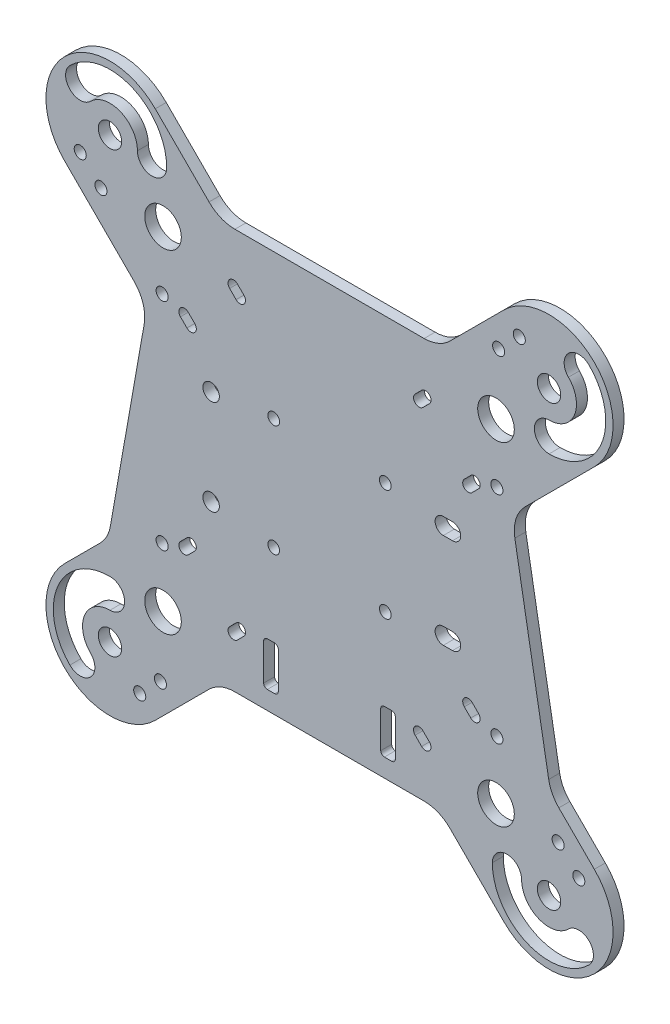
SolidWorks part; units mm, degrees
material "3.0205 (EN-AW 1200)"
ref_plane "Front" through (0, 0, 0) normal (0, 0, 1) x (1, 0, 0)
ref_plane "Top" through (0, 0, 0) normal (0, 1, 0) x (1, 0, 0)
ref_plane "Right" through (0, 0, 0) normal (1, 0, 0) x (0, 0, -1)
other "Massenmittelpunkt"
sketch "Skizze1" plane through (0, 0, 0) normal (0, 0, 1) x (1, 0, 0)
  line L0 (0, -54.3604) -> (0, 62.0087) construction
  line L1 (0, 0) -> (83.9041, 0) construction
  line L2 (30, 54.7487) -> (-30, 54.7487)
  line L3 (-30, 54.7487) -> (-47.6256, 72.3744)
  line L4 (47.6256, -72.3744) -> (30, -54.7487)
  line L5 (-72.3744, 47.6256) -> (-49.7487, 25)
  line L6 (-49.7487, 25) -> (-60.4524, -35.7037)
  line L7 (-60.4524, -35.7037) -> (-72.3744, -47.6256)
  line L8 (60.4524, -35.7037) -> (72.3744, -47.6256)
  line L9 (-47.6256, -72.3744) -> (-30, -54.7487)
  line L10 (-30, -54.7487) -> (30, -54.7487)
  line L11 (49.7487, 25) -> (60.4524, -35.7037)
  line L12 (72.3744, 47.6256) -> (49.7487, 25)
  line L13 (30, 54.7487) -> (47.6256, 72.3744)
  arc A0 (-47.6256, 72.3744) -> (-72.3744, 47.6256) centre (-60, 60) ccw
  arc A1 (-72.3744, -47.6256) -> (-47.6256, -72.3744) centre (-60, -60) ccw
  arc A2 (72.3744, -47.6256) -> (47.6256, -72.3744) centre (60, -60) cw
  arc A3 (47.6256, 72.3744) -> (72.3744, 47.6256) centre (60, 60) cw
  point P26 (0, -54.7487)
  point P35 (0, 54.7487)
  dimension "D5" = 17.5
  dimension "D7" = 17.5
  dimension "D1" = 120
  dimension "D2" = 120
  dimension "D3" = 120
  dimension "D4" = 30
  dimension "D6" = 45
  dimension "D8" = 10
  dimension "D9" = 30
  dimension "D10" = 60
  dimension "D11" = 31.9975
  dimension "D12" = 16.8602
extrude "Aufsatz-Linear austragen1" add sketch "Skizze1" along normal blind 3
sketch "Skizze2" plane through (0, 0, 3) normal (0, 0, 1) x (1, 0, 0)
  line L0 (0, 0) -> (-60, 60) construction
  line L1 (0, 0) -> (0, 84.3112) construction
  line L2 (0, 0) -> (70.8894, 0) construction
  line L3 (0, 0) -> (-60, -60) construction
  arc A0 (-47.6256, 72.3744) -> (-72.3744, 47.6256) centre (-60, 60) ccw construction
  arc A1 (-47.6256, 72.3744) -> (-72.3744, 47.6256) centre (-60, 60) ccw
  circle A2 centre (-60, 60) radius 3.2
  circle A3 centre (-45.5043, 45.5043) radius 5
  circle A4 centre (45.5043, 45.5043) radius 5
  circle A5 centre (60, 60) radius 3.2
  arc A7 (-72.3744, -47.6256) -> (-47.6256, -72.3744) centre (-60, -60) ccw construction
  arc A8 (-72.3744, -47.6256) -> (-47.6256, -72.3744) centre (-60, -60) ccw
  arc A9 (47.6256, -72.3744) -> (72.3744, -47.6256) centre (60, -60) ccw construction
  arc A10 (47.6256, -72.3744) -> (72.3744, -47.6256) centre (60, -60) ccw
  circle A11 centre (-60, -60) radius 3.2
  circle A13 centre (-45.5043, -45.5043) radius 5
  circle A14 centre (45.5043, -45.5043) radius 5
  circle A15 centre (60, -60) radius 3.2
  point P8 (-72.3744, 72.3744)
  point P24 (-72.3744, -72.3744)
  dimension "D1" = 6.4
  dimension "D2" = 10
  dimension "D4" = 6.4
  dimension "D5" = 10
  dimension "D3" = 38
  dimension "D6" = 38
extrude "Schnitt-Linear austragen1" cut sketch "Skizze2" against normal up to surface (3 mm away) contours A3 | A2 | A4 | A14 | A13 | A11 | A5 | A15 region at (-60, 60, 3) region at (-45.5043, 45.5043, 3) region at (45.5043, 45.5043, 3) region at (-60, -60, 3) region at (-45.5043, -45.5043, 3) region at (45.5043, -45.5043, 3) up to face at (0, -1.338, 0)
sketch "Skizze3" plane through (0, 0, 3) normal (0, 0, 1) x (1, 0, 0)
  line L0 (0, 0) -> (0, 66.0751) construction
  line L1 (0, 0) -> (91.439, 0) construction
  line L2 (-60, 60) -> (-93.2508, 93.2508) construction
  line L5 (-60, 60) -> (-28.4544, 60) construction
  line L6 (60, 60) -> (89.3075, 89.3075) construction
  line L7 (60, 60) -> (60, 26.1237) construction
  line L8 (60, -60) -> (74.6096, -74.6096) construction
  line L9 (-60, -60) -> (-91.9373, -91.9373) construction
  line L12 (60, -60) -> (20.7483, -60) construction
  line L13 (-60, -60) -> (-60, -22.984) construction
  arc A0 (65.3033, 65.3033) -> (70.9602, 70.9602) centre (68.1317, 68.1317) cw
  circle A1 centre (-60, 60) radius 3.2 construction
  circle A2 centre (-60, 60) radius 3.2
  arc A3 (-70.9602, 70.9602) -> (-44.5, 60) centre (-60, 60) cw
  arc A4 (-65.3033, 65.3033) -> (-52.5, 60) centre (-60, 60) cw
  arc A5 (-70.9602, 70.9602) -> (-65.3033, 65.3033) centre (-68.1317, 68.1317) ccw
  arc A6 (-52.5, 60) -> (-44.5, 60) centre (-48.5, 60) ccw
  arc A8 (60, 52.5) -> (65.3033, 65.3033) centre (60, 60) ccw
  arc A9 (60, 44.5) -> (60, 52.5) centre (60, 48.5) cw
  arc A10 (60, 44.5) -> (70.9602, 70.9602) centre (60, 60) ccw
  arc A12 (65.3033, -65.3033) -> (52.5, -60) centre (60, -60) cw
  arc A13 (70.9602, -70.9602) -> (44.5, -60) centre (60, -60) cw
  arc A14 (44.5, -60) -> (52.5, -60) centre (48.5, -60) cw
  arc A15 (65.3033, -65.3033) -> (70.9602, -70.9602) centre (68.1317, -68.1317) cw
  arc A16 (-70.9602, -70.9602) -> (-60, -44.5) centre (-60, -60) cw
  arc A17 (-65.3033, -65.3033) -> (-60, -52.5) centre (-60, -60) cw
  arc A18 (-70.9602, -70.9602) -> (-65.3033, -65.3033) centre (-68.1317, -68.1317) ccw
  arc A19 (-60, -44.5) -> (-60, -52.5) centre (-60, -48.5) cw
  dimension "D3" = 4
  dimension "D4" = 11.5
  dimension "D5" = 4
  dimension "D7" = 4
  dimension "D11" = 4
  dimension "D1" = 45
  dimension "D2" = 11.5
  dimension "D6" = 45
  dimension "D8" = 11.5
  dimension "D9" = 45
  dimension "D10" = 45
  dimension "D12" = 11.5
extrude "Schnitt-Linear austragen2" cut sketch "Skizze3" against normal up to surface (3 mm away) up to face at (-56.8, 60, 0)
ref_axis "Achse1" through (0, 0, -80.9) along (0, 0, 1)
sketch "Skizze5" plane through (0, 0, 3) normal (0, 0, 1) x (1, 0, 0)
  line L0 (31.11, -13) -> (33.61, -13) construction
  line L1 (-15.25, -15.25) -> (15.25, -15.25) construction
  line L2 (-15.25, -15.25) -> (-15.25, 15.25) construction
  line L3 (-15.25, 15.25) -> (15.25, 15.25) construction
  line L4 (15.25, -15.25) -> (15.25, 15.25) construction
  line L5 (-15.25, -15.25) -> (15.25, 15.25) construction
  line L6 (-15.25, 15.25) -> (15.25, -15.25) construction
  line L7 (-32.36, -13) -> (32.36, -13) construction
  line L8 (-32.36, -13) -> (-32.36, 13) construction
  line L9 (-32.36, 13) -> (32.36, 13) construction
  line L10 (32.36, -13) -> (32.36, 13) construction
  line L11 (-32.36, -13) -> (32.36, 13) construction
  line L12 (-32.36, 13) -> (32.36, -13) construction
  line L13 (31.11, 13) -> (33.61, 13) construction
  line L16 (31.11, 15.25) -> (33.61, 15.25)
  line L17 (31.11, 10.75) -> (33.61, 10.75)
  line L18 (31.11, -10.75) -> (33.61, -10.75)
  line L19 (31.11, -15.25) -> (33.61, -15.25)
  circle A0 centre (-15.25, 15.25) radius 1.6
  circle A1 centre (15.25, 15.25) radius 1.6
  circle A2 centre (15.25, -15.25) radius 1.6
  circle A3 centre (-15.25, -15.25) radius 1.6
  circle A4 centre (-32.36, 13) radius 2.25
  circle A7 centre (-32.36, -13) radius 2.25
  arc A10 (31.11, 15.25) -> (31.11, 10.75) centre (31.11, 13) ccw
  arc A11 (33.61, 10.75) -> (33.61, 15.25) centre (33.61, 13) ccw
  arc A12 (31.11, -10.75) -> (31.11, -15.25) centre (31.11, -13) ccw
  arc A13 (33.61, -15.25) -> (33.61, -10.75) centre (33.61, -13) ccw
  point P0 (0, 0)
  point P7 (0, 0)
  point P22 (32.36, 13)
  point P29 (32.36, -13)
  point P34 (28.86, 13)
  point P35 (35.86, 13)
  dimension "D3" = 3.2
  dimension "D4" = 4
  dimension "D7" = 4.5
  dimension "D8" = 4.5
  dimension "D9" = 4.5
  dimension "D11" = 7
  dimension "D1" = 30.5
  dimension "D2" = 30.5
  dimension "D5" = 64.72
  dimension "D6" = 26
extrude "Schnitt-Linear austragen3" cut sketch "Skizze5" against normal up to surface (3 mm away) up to face at (57.6646, -65.6381, 0)
sketch "Skizze6" plane through (0, 0, 3) normal (0, 0, 1) x (1, 0, 0)
  line L0 (-60, 60) -> (60, -60) construction
  line L1 (60, 60) -> (-60, -60) construction
ref_point "Punkt1"
ref_axis "Achse2" through (0, 0, 3) along (0, 0, 1)
sketch "Skizze7" plane through (0, 0, 3) normal (0, 0, 1) x (1, 0, 0)
  line L3 (-45.7487, 29.5) -> (45.7487, 29.5) construction
  line L5 (-45.7487, 29.5) -> (-45.7487, -29.5) construction
  line L9 (-45.7487, -29.5) -> (45.7487, -29.5) construction
  line L10 (45.7487, -29.5) -> (45.7487, 29.5) construction
  line L11 (0, 36.7682) -> (0, -20.7433) construction
  line L12 (0, 0) -> (-25.0088, 0) construction
  circle A8 centre (-45.7487, 29.5) radius 0.5
  circle A9 centre (-45.7487, -29.5) radius 0.5
  circle A10 centre (45.7487, -29.5) radius 0.5
  circle A11 centre (45.7487, 29.5) radius 0.5
  dimension "D3" = 1
  dimension "D1" = 4
  dimension "D2" = 59
extrude "Schnitt-Linear austragen4" cut sketch "Skizze7" against normal through all
fillet "Verrundung1" radius 10 8 edges at (-60.4524, -35.7037, 1.5) (-49.7487, 25, 1.5) (-30, 54.7487, 1.5) (30, 54.7487, 1.5) (60.4524, -35.7037, 1.5) (49.7487, 25, 1.5) (30, -54.7487, 1.5) (-30, -54.7487, 1.5)
sketch "Skizze8" plane through (0, 0, 3) normal (0, 0, 1) x (1, 0, 0)
  line L0 (72.3744, -72.3744) -> (-72.3744, 72.3744) construction
  line L1 (72.3744, 72.3744) -> (-72.3744, -72.3744) construction
  line L2 (20.2, -45.3527) -> (41.1281, -24.4247) construction
  line L3 (0, 14.4257) -> (0, -17.0343) construction
  line L4 (-16.3829, 0) -> (7.5205, 0) construction
  line L5 (-39.6707, -27.6499) -> (-37.9029, -25.8821) construction
  line L6 (24.4679, -39.3171) -> (26.2357, -41.0849) construction
  line L7 (25.5285, -38.2565) -> (27.2963, -40.0242)
  line L8 (23.4072, -40.3778) -> (25.175, -42.1456)
  line L9 (39.6707, -27.6499) -> (37.9029, -25.8821) construction
  line L10 (38.61, -28.7105) -> (36.8423, -26.9428)
  line L11 (40.7313, -26.5892) -> (38.9636, -24.8214)
  line L12 (-38.61, -28.7105) -> (-36.8423, -26.9428)
  line L13 (-40.7313, -26.5892) -> (-38.9636, -24.8214)
  line L14 (-24.4679, -39.3171) -> (-26.2357, -41.0849) construction
  line L15 (-25.5285, -38.2565) -> (-27.2963, -40.0242)
  line L16 (-23.4072, -40.3778) -> (-25.175, -42.1456)
  line L17 (-24.4679, 39.3171) -> (-26.2357, 41.0849) construction
  line L18 (-25.5285, 38.2565) -> (-27.2963, 40.0242)
  line L19 (-23.4072, 40.3778) -> (-25.175, 42.1456)
  line L20 (-39.6707, 27.6499) -> (-37.9029, 25.8821) construction
  line L21 (-38.61, 28.7105) -> (-36.8423, 26.9428)
  line L22 (-40.7313, 26.5892) -> (-38.9636, 24.8214)
  line L23 (39.6707, 27.6499) -> (37.9029, 25.8821) construction
  line L24 (38.61, 28.7105) -> (36.8423, 26.9428)
  line L25 (40.7313, 26.5892) -> (38.9636, 24.8214)
  line L26 (24.4679, 39.3171) -> (26.2357, 41.0849) construction
  line L27 (25.5285, 38.2565) -> (27.2963, 40.0242)
  line L28 (23.4072, 40.3778) -> (25.175, 42.1456)
  arc A0 (47.6256, -72.3744) -> (72.3744, -47.6256) centre (60, -60) ccw construction
  arc A1 (-47.6256, 72.3744) -> (-72.3744, 47.6256) centre (-60, 60) ccw construction
  arc A2 (72.3744, 47.6256) -> (47.6256, 72.3744) centre (60, 60) ccw construction
  arc A3 (-72.3744, -47.6256) -> (-47.6256, -72.3744) centre (-60, -60) ccw construction
  arc A18 (25.5285, -38.2565) -> (23.4072, -40.3778) centre (24.4679, -39.3171) ccw
  arc A19 (25.175, -42.1456) -> (27.2963, -40.0242) centre (26.2357, -41.0849) ccw
  arc A20 (38.61, -28.7105) -> (40.7313, -26.5892) centre (39.6707, -27.6499) ccw
  arc A21 (38.9636, -24.8214) -> (36.8423, -26.9428) centre (37.9029, -25.8821) ccw
  arc A22 (-38.61, -28.7105) -> (-40.7313, -26.5892) centre (-39.6707, -27.6499) cw
  arc A23 (-38.9636, -24.8214) -> (-36.8423, -26.9428) centre (-37.9029, -25.8821) cw
  arc A24 (-25.5285, -38.2565) -> (-23.4072, -40.3778) centre (-24.4679, -39.3171) cw
  arc A25 (-25.175, -42.1456) -> (-27.2963, -40.0242) centre (-26.2357, -41.0849) cw
  arc A26 (-25.5285, 38.2565) -> (-23.4072, 40.3778) centre (-24.4679, 39.3171) ccw
  arc A27 (-25.175, 42.1456) -> (-27.2963, 40.0242) centre (-26.2357, 41.0849) ccw
  arc A28 (-38.61, 28.7105) -> (-40.7313, 26.5892) centre (-39.6707, 27.6499) ccw
  arc A29 (-38.9636, 24.8214) -> (-36.8423, 26.9428) centre (-37.9029, 25.8821) ccw
  arc A30 (38.61, 28.7105) -> (40.7313, 26.5892) centre (39.6707, 27.6499) cw
  arc A31 (38.9636, 24.8214) -> (36.8423, 26.9428) centre (37.9029, 25.8821) cw
  arc A32 (25.5285, 38.2565) -> (23.4072, 40.3778) centre (24.4679, 39.3171) cw
  arc A33 (25.175, 42.1456) -> (27.2963, 40.0242) centre (26.2357, 41.0849) cw
  point P16 (0, 0)
  point P18 (25.3518, -40.201)
  point P21 (38.7868, -26.766)
  point P24 (45.5043, -45.5043)
  point P34 (-38.7868, -26.766)
  point P41 (-25.3518, -40.201)
  point P55 (-25.3518, 40.201)
  point P63 (-38.7868, 26.766)
  point P70 (38.7868, 26.766)
  point P77 (25.3518, 40.201)
  point P82 (23.4072, -38.2565)
  point P83 (27.2963, -42.1456)
  dimension "D2" = 5.5
  dimension "D1" = 3
  dimension "D3" = 18
  dimension "D5" = 9
  dimension "D4" = 16
extrude "ECSs Befestigung" cut sketch "Skizze8" against normal through all
sketch "Skizze9" plane through (0, 0, 3) normal (0, 0, 1) x (1, 0, 0)
  line L0 (47.6256, 72.3744) -> (32.9289, 57.6777) construction
  line L4 (47.6256, 72.3744) -> (53.5852, 66.4148) construction
  circle A0 centre (46.2114, 62.4749) radius 0.5
  dimension "D5" = 1
  dimension "D1" = 6
  dimension "D6" = 8
extrude "Schnitt-Linear austragen6" cut sketch "Skizze9" against normal through all
pattern_circular "Kreismuster1" count 4 over 360 about axis through (0, 0, 3) along (0, 0, 1) of "Schnitt-Linear austragen6"
sketch "Skizze10" plane through (0, 0, 3) normal (0, 0, 1) x (1, 0, 0)
  line L0 (0, 0) -> (0, -69.4761) construction
  line L1 (-18, -37.7487) -> (-14, -37.7487)
  line L2 (-18, -37.7487) -> (-18, -49.7487)
  line L3 (-18, -49.7487) -> (-14, -49.7487)
  line L4 (-14, -37.7487) -> (-14, -49.7487)
  line L5 (18, -37.7487) -> (14, -37.7487)
  line L6 (18, -37.7487) -> (18, -49.7487)
  line L7 (18, -49.7487) -> (14, -49.7487)
  line L8 (14, -37.7487) -> (14, -49.7487)
  line L9 (-25.8579, -54.7487) -> (25.8579, -54.7487) construction
  dimension "D1" = 4
  dimension "D2" = 28
  dimension "D3" = 12
  dimension "D4" = 5
extrude "Befestigung SpannTester" cut sketch "Skizze10" against normal through all
fillet "Verrundung2" radius 1 8 edges at (-14, -49.7487, 1.5) (18, -49.7487, 1.5) (14, -49.7487, 1.5) (-18, -49.7487, 1.5) (14, -37.7487, 1.5) (-18, -37.7487, 1.5) (18, -37.7487, 1.5) (-14, -37.7487, 1.5)
sketch "Skizze13" plane through (0, 0, 3) normal (0, 0, 1) x (1, 0, 0)
  line L0 (0, 0) -> (0, 19.7453) construction
  line L1 (-6, 30) -> (6, 30)
  line L2 (-9, 27) -> (-9, 10.5)
  line L3 (-6, -30) -> (6, -30)
  line L4 (9, 27) -> (9, 10.5)
  line L5 (-22, 7.5) -> (-12, 7.5)
  line L6 (-25, 4.5) -> (-25, -4.5)
  line L7 (-22, -7.5) -> (-12, -7.5)
  line L8 (25, 4.5) -> (25, -4.5)
  line L9 (0, 0) -> (27.175, 0) construction
  line L10 (12, 7.5) -> (22, 7.5)
  line L11 (-9, -10.5) -> (-9, -27)
  line L12 (12, -7.5) -> (22, -7.5)
  line L13 (9, -10.5) -> (9, -27)
  arc A0 (6, -30) -> (9, -27) centre (6, -27) ccw
  arc A1 (-6, -30) -> (-9, -27) centre (-6, -27) cw
  arc A2 (-22, -7.5) -> (-25, -4.5) centre (-22, -4.5) cw
  arc A3 (-25, 4.5) -> (-22, 7.5) centre (-22, 4.5) cw
  arc A4 (-9, 10.5) -> (-12, 7.5) centre (-12, 10.5) cw
  arc A5 (-12, -7.5) -> (-9, -10.5) centre (-12, -10.5) cw
  arc A6 (12, -7.5) -> (9, -10.5) centre (12, -10.5) ccw
  arc A7 (25, -4.5) -> (22, -7.5) centre (22, -4.5) cw
  arc A8 (25, 4.5) -> (22, 7.5) centre (22, 4.5) ccw
  arc A9 (9, 10.5) -> (12, 7.5) centre (12, 10.5) ccw
  arc A10 (9, 27) -> (6, 30) centre (6, 27) ccw
  arc A11 (-9, 27) -> (-6, 30) centre (-6, 27) cw
  point P22 (-25, -7.5)
  point P25 (-25, 7.5)
  point P32 (9, -7.5)
  point P35 (25, -7.5)
  point P42 (9, 30)
  point P45 (-9, 30)
  dimension "D5" = 3
  dimension "D1" = 18
  dimension "D2" = 15
  dimension "D3" = 50
  dimension "D4" = 60
extrude "Schnitt-Linear austragen7" [suppressed] cut sketch "Skizze13" against normal through all
hole_wizard "M4 Gewindebohrung1" positions "Skizze14" profile "Skizze15" tap size "M4" standard "DIN" end condition through all
sketch "Skizze14" plane through (0, 0, 3) normal (0, 0, 1) x (1, 0, 0)
  point P0 (-45.7487, 29.5)
  point P3 (-62.4749, 46.2114)
  point P6 (-46.2114, -62.4749)
  point P9 (-45.7487, -29.5)
  point P12 (45.7487, 29.5)
  point P15 (45.7487, -29.5)
  point P18 (62.4749, -46.2114)
  point P21 (46.2114, 62.4749)
sketch "Skizze15" plane through (-45.7487, 29.5, 3) normal (1, 0, 0) x (0, -1, 0)
  line L0 (0, 0) -> (0, 3)
  line L1 (0, 3) -> (1.65, 3)
  line L2 (1.65, 3) -> (1.65, 0)
  line L5 (1.65, 0) -> (0, 0)
  line L11 (0, -6.35) -> (0, 107.95) construction
  dimension "Bohrerdurchmesser" = 3.3
  dimension "Bohrungstiefe" = 3
cosmetic thread "Bohrungsgewinde1" parameters "D1"=6, "D2"=4.3
cosmetic thread "Bohrungsgewinde2" parameters "D1"=6, "D2"=4.3
cosmetic thread "Bohrungsgewinde3" parameters "D1"=6, "D2"=4.3
cosmetic thread "Bohrungsgewinde4" parameters "D1"=6, "D2"=4.3
cosmetic thread "Bohrungsgewinde5" parameters "D1"=6, "D2"=4.3
cosmetic thread "Bohrungsgewinde6" parameters "D1"=6, "D2"=4.3
cosmetic thread "Bohrungsgewinde7" parameters "D1"=6, "D2"=4.3
cosmetic thread "Bohrungsgewinde8" parameters "D1"=6, "D2"=4.3
sketch "Skizze16" plane through (0, 0, 3) normal (0, 0, 1) x (1, 0, 0)
  line L0 (-47.6256, -72.3744) -> (-32.9289, -57.6777) construction
  line L1 (-47.6256, -72.3744) -> (-56.8677, -63.1323) construction
  circle A0 centre (-51.8683, -68.1317) radius 0.5
  circle A1 centre (-68.1317, 51.8683) radius 0.5
  circle A2 centre (51.8683, 68.1317) radius 0.5
  circle A3 centre (68.1317, -51.8683) radius 0.5
  point P4 (-46.2114, -62.4749)
  point P15 (0, 0)
  dimension "D3" = 1
  dimension "D1" = 6
  dimension "D4" = 4
extrude "Schnitt-Linear austragen8" cut sketch "Skizze16" against normal through all
hole_wizard "M4 Gewindebohrung2" positions "Skizze17" profile "Skizze18" tap size "M4" standard "DIN" end condition through all
sketch "Skizze17" plane through (0, 0, 3) normal (0, 0, 1) x (1, 0, 0)
  point P0 (-51.8683, -68.1317)
  point P3 (-68.1317, 51.8683)
  point P6 (51.8683, 68.1317)
  point P9 (68.1317, -51.8683)
sketch "Skizze18" plane through (-51.8683, -68.1317, 3) normal (1, 0, 0) x (0, -1, 0)
  line L0 (0, 0) -> (0, 3)
  line L1 (0, 3) -> (1.65, 3)
  line L2 (1.65, 3) -> (1.65, 0)
  line L5 (1.65, 0) -> (0, 0)
  line L11 (0, -6.35) -> (0, 107.95) construction
  dimension "Bohrerdurchmesser" = 3.3
  dimension "Bohrungstiefe" = 3
cosmetic thread "Bohrungsgewinde9" parameters "D2"=4
cosmetic thread "Bohrungsgewinde10" parameters "D2"=4
cosmetic thread "Bohrungsgewinde11" parameters "D2"=4
cosmetic thread "Bohrungsgewinde12" parameters "D2"=4
